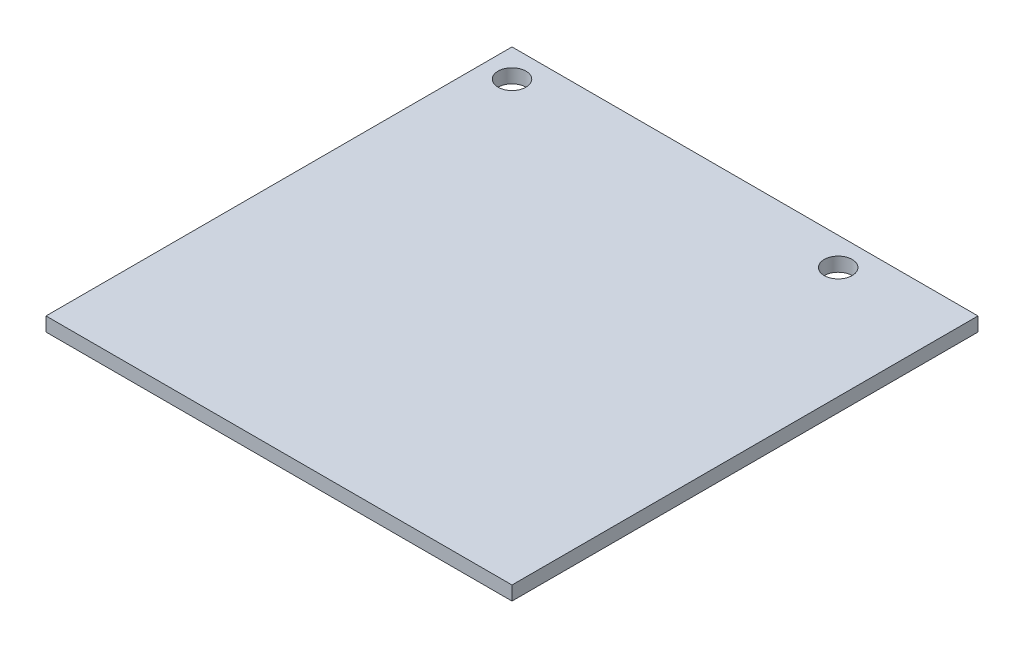
SolidWorks part; units mm, degrees
ref_plane "Front Plane" through (0, 0, 0) normal (0, 0, 1) x (1, 0, 0)
ref_plane "Top Plane" through (0, 0, 0) normal (0, 1, 0) x (1, 0, 0)
ref_plane "Right Plane" through (0, 0, 0) normal (1, 0, 0) x (0, 0, -1)
sketch "Sketch1" plane through (0, 0, 0) normal (0, 1, 0) x (1, 0, 0)
  line L1 (0, 0) -> (50, 0)
  line L2 (0, 0) -> (0, 50)
  line L3 (0, 50) -> (50, 50)
  line L4 (50, 0) -> (50, 50)
  circle A0 centre (38, 47) radius 1.5
  circle A1 centre (3, 47) radius 1.5
  dimension "D1" = 3
  dimension "D2" = 35
  dimension "D3" = 3
  dimension "D4" = 3
  dimension "D5" = 50
  dimension "D6" = 50
extrude "Boss-Extrude1" add sketch "Sketch1" along normal blind 1.5
